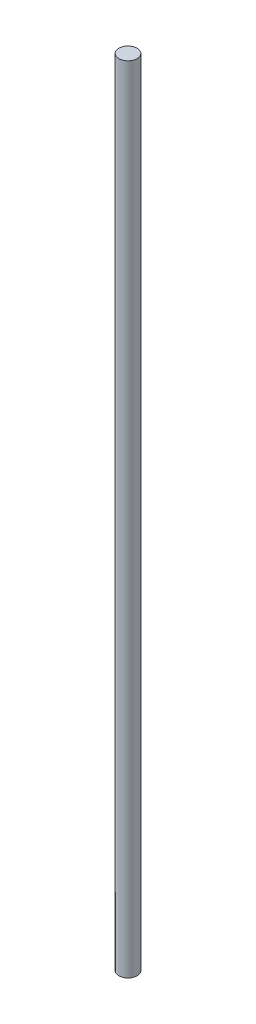
SolidWorks part; units mm, degrees
ref_plane "Front Plane" through (0, 0, 0) normal (0, 0, 1) x (1, 0, 0)
ref_plane "Top Plane" through (0, 0, 0) normal (0, 1, 0) x (1, 0, 0)
ref_plane "Right Plane" through (0, 0, 0) normal (1, 0, 0) x (0, 0, -1)
sketch "Sketch1" plane through (0, 0, 0) normal (0, 1, 0) x (1, 0, 0)
  circle A0 centre (0, 0) radius 4
  dimension "D1" = 8
extrude "Boss-Extrude1" add sketch "Sketch1" along normal blind 350
equation "\"Y-ROD-SPACING\"=75"
equation "\"Y-BED-OFFSET\"=2"
equation "\"Y-BED-ROD-INSET\"=3.5"
equation "\"T-SLOT-NUT-FILLET-RADIUS\"=0.5"
equation "\"T-SLOT-SCREW-SHAFT-RADIUS\"=1.55"
equation "\"T-SLOT-SCREW-SHAFT-CUTOUT-LENGTH\"=11"
equation "\"T-SLOT-NUT-DEPTH\"=3.5"
equation "\"T-SLOT-NUT-WIDTH\"=2.85"
equation "\"T-SLOT-NUT-END-DISTANCE\"=8"
equation "\"ACRYLIC-THICKNESS\"=10"
equation "\"ACRYLIC-TAB-CUTOUT-SIZE\"=\"ACRYLIC-THICKNESS\"+\"ACRYLIC-TAB-TOLERANCE\"*2"
equation "\"ACRYLIC-TAB-WIDTH\"=\"ACRYLIC-THICKNESS\""
equation "\"ACRYLIC-M3-HOLE\"=2.9"
equation "\"SMOOTHROD-CAP-SCREW-DISTANCE\"=20"
equation "\"FRAME-WIDTH-INNER\"=370"
equation "\"NEMA17-HOLE-SPACING\"=31"
equation "\"NEMA17-CENTRAL-CUTOUT\"=22.5"
equation "\"Z-BRACKET-REACH\"=57"
equation "\"TOP-BRACKET-SPACING\"=40"
equation "\"SMOOTHROD-X-LENGTH\"=350"
equation "\"SMOOTHROD-Y-LENGTH\"=350"
equation "\"SMOOTHROD-Z-LENGTH\"=350"
equation "\"SMOOTHROD-TIGHTENING-HEADROOM\"=.25"
equation "\"LEADSCREW-Z-LENGTH\"=300"
equation "\"D1@Boss-Extrude1\"=\"SMOOTHROD-Z-LENGTH\""
